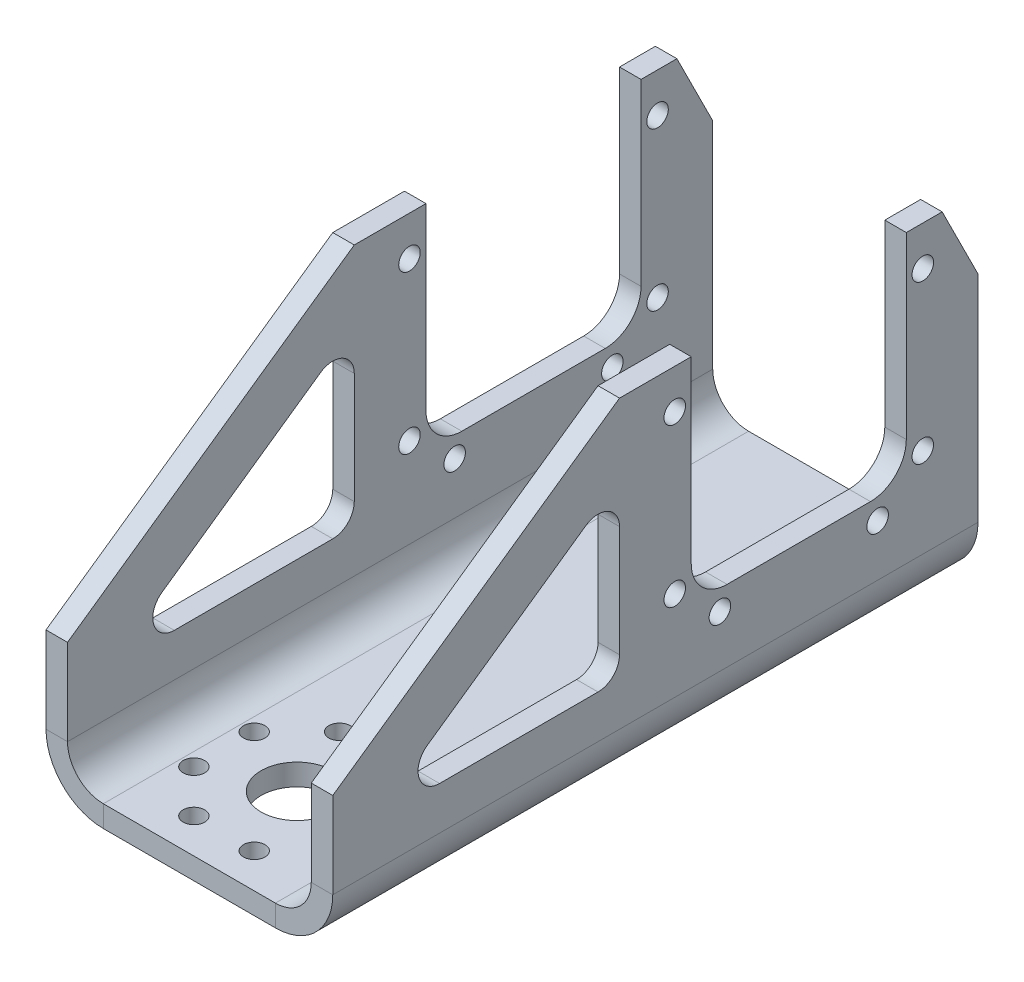
SolidWorks part; units mm, degrees
note: The reader was unsure of these and kept them because the rebuilt part matched: bend radius of "Basisbiegung1", "Basisbiegung2".
material "Alu Künz"
ref_plane "Ebene vorne" through (0, 0, 0) normal (0, 0, 1) x (1, 0, 0)
ref_plane "Ebene oben" through (0, 0, 0) normal (0, 1, 0) x (1, 0, 0)
ref_plane "Ebene rechts" through (0, 0, 0) normal (1, 0, 0) x (0, 0, -1)
sketch "Skizze1" plane through (0, 0, 0) normal (0, 0, 1) x (1, 0, 0)
  line L0 (0, 0) -> (0, 50) construction
  line L1 (-17, 45) -> (-17, 0)
  line L2 (-17, 0) -> (17, 0)
  line L3 (17, 45) -> (17, 0)
  dimension "D1" = 34
  dimension "D2" = 45
sheet metal parameters "Blech1" thickness 3 parameters "D1"=5
base flange "Basis-Blech1" sketch "Skizze1" end condition mid plane depth 90 reverse direction no thickness 3 reverse thickness direction yes bend radius 5
bend "Basisbiegung1" bend radius 5 bend angle 90 parameters "D5"=1
bend "Basisbiegung2" bend radius 5 bend angle 90 parameters "D5"=2
sketch "Skizze3" plane through (0, 0, 0) normal (0, 1, 0) x (1, 0, 0)
  line L0 (0, 0) -> (0, -30) construction
  line L1 (12, -45) -> (-12, -45) construction
  circle A0 centre (0, -30) radius 5
  dimension "D1" = 10
  dimension "D2" = 15
extrude "Schnitt-Linear austragen2" cut sketch "Skizze3" against normal through all normal cut yes
sketch "Skizze2" plane through (0, 0, 0) normal (1, 0, 0) x (0, 0, -1)
  line L0 (-45, 45) -> (45, 45) construction
  line L1 (35, 45) -> (5, 45)
  line L2 (35, 45) -> (35, 20)
  line L3 (30, 15) -> (10, 15)
  line L4 (5, 45) -> (5, 20)
  line L5 (45, 5) -> (45, 45) construction
  line L6 (-45, 45) -> (-5, 45)
  line L7 (-5, 45) -> (-45, 17)
  line L8 (-45, 5) -> (-45, 45) construction
  line L9 (-45, 17) -> (-45, 45)
  line L10 (-45, -3) -> (45, -3) construction
  line L11 (45, 45) -> (40, 45)
  line L12 (40, 45) -> (45, 35)
  line L13 (45, 35) -> (45, 45)
  line L14 (-5, 29.4728) -> (-5, 14)
  line L15 (-8, 11) -> (-30.104, 11)
  line L16 (-31.8244, 16.4577) -> (-9.7204, 31.9305)
  line L17 (-45, 5) -> (45, 5) construction
  arc A0 (10, 15) -> (5, 20) centre (10, 20) cw
  arc A1 (35, 20) -> (30, 15) centre (30, 20) cw
  arc A2 (-30.104, 11) -> (-31.8244, 16.4577) centre (-30.104, 14) cw
  arc A3 (-5, 14) -> (-8, 11) centre (-8, 14) cw
  arc A4 (-5, 29.4728) -> (-9.7204, 31.9305) centre (-8, 29.4728) ccw
  point P18 (5, 15)
  dimension "D6" = 5
  dimension "D12" = 3
  dimension "D1" = 10
  dimension "D2" = 30
  dimension "D3" = 30
  dimension "D4" = 20
  dimension "D5" = 10
  dimension "D7" = 5
  dimension "D8" = 10
  dimension "D9" = 6
  dimension "D10" = 10
  dimension "D11" = 8
extrude "Schnitt-Linear austragen1" cut sketch "Skizze2" against normal through all both and the other way through all normal cut yes
sketch "Skizze4" plane through (0, 0, 0) normal (1, 0, 0) x (0, 0, -1)
  line L0 (37.3, 39.5) -> (37.3, 17.5) construction
  line L1 (37.3, 17.5) -> (2.7, 17.5) construction
  line L2 (2.7, 17.5) -> (2.7, 39.5) construction
  line L3 (31, 12.2) -> (9, 12.2) construction
  line L4 (20, 17.5) -> (20, 12.2) construction
  line L5 (20, 15) -> (20, 17.5) construction
  line L6 (10, 15) -> (30, 15) construction
  line L7 (35, 45) -> (40, 45) construction
  point P0 (37.3, 39.5)
  point P1 (37.3, 17.5)
  point P2 (31, 12.2)
  point P3 (9, 12.2)
  point P4 (2.7, 17.5)
  point P5 (2.7, 39.5)
  dimension "D1" = 5.5
  dimension "D2" = 22
  dimension "D3" = 34.6
  dimension "D4" = 22
  dimension "D5" = 5.3
hole_wizard "Ø3.0 (3) Durchmesser Bohrung1" positions "Skizze5" profile "Skizze6" hole size "Ø3.0" standard "KUENZ_DIN" end condition through all
sketch "Skizze5" plane through (-20, 0, 0) normal (-1, 0, 0) x (0, 0, 1)
  point P0 (-37.3, 39.5)
  point P3 (-37.3, 17.5)
  point P6 (-31, 12.2)
  point P9 (-9, 12.2)
  point P12 (-2.7, 17.5)
  point P15 (-2.7, 39.5)
sketch "Skizze6" plane through (-20, 39.5, -37.3) normal (0, 1, 0) x (0, 0, 1)
  line L0 (0, 0) -> (0, 40)
  line L1 (0, 40) -> (1.5, 40)
  line L2 (1.5, 40) -> (1.5, 0)
  line L5 (1.5, 0) -> (0, 0)
  line L11 (0, -6.35) -> (0, 107.95) construction
  dimension "Bohrerdurchmesser" = 3
  dimension "Bohrungstiefe" = 40
sketch "Skizze7" plane through (0, 0, 0) normal (0, 1, 0) x (1, 0, 0)
  line L0 (0, -30) -> (4.2095, -40.1627) construction
  line L1 (12, -45) -> (12, 45) construction
  line L2 (0, -30) -> (-4.2095, -40.1627) construction
  line L3 (0, -30) -> (-10.1627, -34.2095) construction
  line L4 (0, -30) -> (-10.1627, -25.7905) construction
  line L5 (0, -30) -> (-4.2095, -19.8373) construction
  line L6 (0, -30) -> (4.2095, -19.8373) construction
  line L7 (0, -30) -> (10.1627, -25.7905) construction
  line L8 (0, -30) -> (10.1627, -34.2095) construction
  point P14 (0, -30)
  dimension "D1" = 11
  dimension "D2" = 22.5
  dimension "D3" = 8
hole_wizard "Ø3.0 (3) Durchmesser Bohrung2" positions "Skizze8" profile "Skizze9" hole size "Ø3.0" standard "KUENZ_DIN" end condition through all
sketch "Skizze8" plane through (0, 0, 0) normal (0, 1, 0) x (1, 0, 0)
  point P0 (10.1627, -25.7905)
  point P3 (4.2095, -19.8373)
  point P6 (-4.2095, -19.8373)
  point P8 (-10.1627, -25.7905)
  point P11 (-10.1627, -34.2095)
  point P14 (-4.2095, -40.1627)
  point P17 (4.2095, -40.1627)
  point P20 (10.1627, -34.2095)
sketch "Skizze9" plane through (10.1627, 0, 25.7905) normal (1, 0, 0) x (0, 0, 1)
  line L0 (0, 0) -> (0, 3)
  line L1 (0, 3) -> (1.5, 3)
  line L2 (1.5, 3) -> (1.5, 0)
  line L5 (1.5, 0) -> (0, 0)
  line L11 (0, -6.35) -> (0, 107.95) construction
  dimension "Bohrerdurchmesser" = 3
  dimension "Bohrungstiefe" = 3
flat pattern "Abwicklung1" [suppressed]
sketch "Biegung-Linien1" plane through (-47, 0, 0) normal (1, 0, 0) x (0, 0, -1)
  line L0 (-115, -2.8949) -> (115, -2.8949) construction
  line L1 (-115, 91.3153) -> (115, 91.3153) construction
  line L2 (-115, -2.8949) -> (115, -2.8949) construction
  line L3 (-115, 91.3153) -> (115, 91.3153) construction
sketch3d "Rahmen1" [suppressed]
  line L0 (230, 0, 0) -> (230, 388.4204, 0) construction
  line L1 (0, 0, 0) -> (0, 388.4204, 0) construction
  line L2 (230, 0, 0) -> (0, 0, 0) construction
  line L3 (230, 388.4204, 0) -> (0, 388.4204, 0) construction
bend of the flat pattern "Abwickeln-<Basisbiegung1>1"
bend of the flat pattern "Abwickeln-<Basisbiegung2>1"
